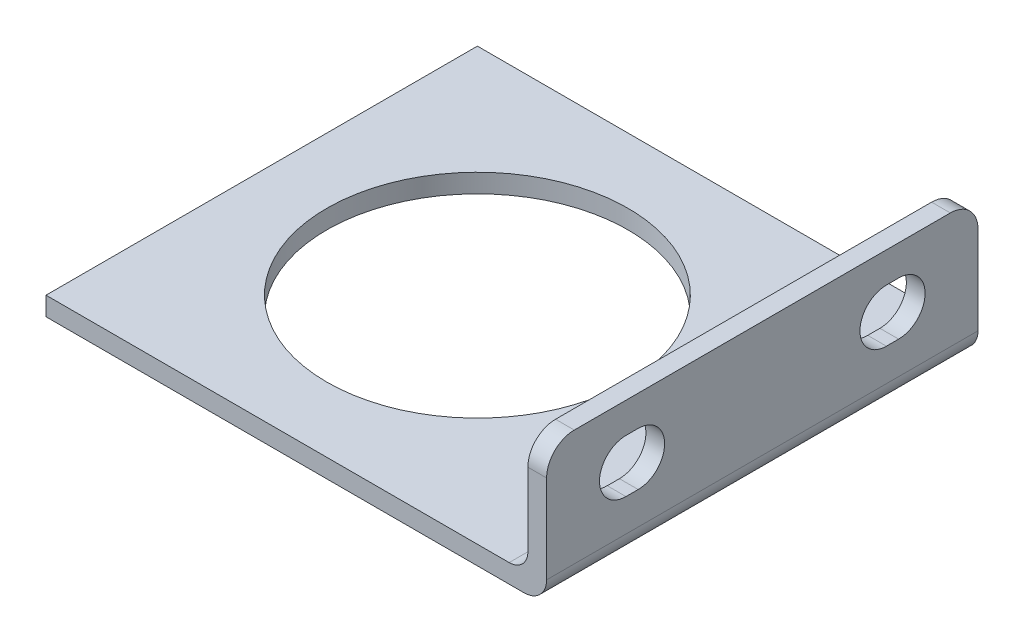
SolidWorks part; units mm, degrees
ref_plane "前视基准面" through (0, 0, 0) normal (0, 0, 1) x (1, 0, 0)
ref_plane "上视基准面" through (0, 0, 0) normal (0, 1, 0) x (1, 0, 0)
ref_plane "右视基准面" through (0, 0, 0) normal (1, 0, 0) x (0, 0, -1)
sketch "草图1" plane through (0, 0, 0) normal (0, 0, 1) x (1, 0, 0)
  line L0 (-26.5, 0) -> (32.24, 0)
  line L1 (35, 2.76) -> (35, 17)
  line L2 (35, 17) -> (32.7, 17)
  line L3 (32.7, 17) -> (32.7, 4.6)
  line L4 (30.4, 2.3) -> (-26.5, 2.3)
  line L5 (-26.5, 2.3) -> (-26.5, 0)
  arc A0 (32.24, 0) -> (35, 2.76) centre (32.24, 2.76) ccw
  arc A1 (32.7, 4.6) -> (30.4, 2.3) centre (30.4, 4.6) cw
extrude "凸台-拉伸1" add sketch "草图1" against normal blind 26.5 and the other way blind 26.5
ref_plane "基准面4" through (35, 0, 0) normal (1, 0, 0) x (0, 0, -1)
sketch "草图2" plane through (35, 0, 0) normal (1, 0, 0) x (0, 0, -1)
  line L0 (-16.75, 6.75) -> (-15.25, 6.75)
  line L1 (-15.25, 13.25) -> (-16.75, 13.25)
  arc A0 (-20, 10) -> (-16.75, 6.75) centre (-16.75, 10) ccw
  arc A1 (-15.25, 6.75) -> (-12, 10) centre (-15.25, 10) ccw
  arc A2 (-12, 10) -> (-15.25, 13.25) centre (-15.25, 10) ccw
  arc A3 (-16.75, 13.25) -> (-20, 10) centre (-16.75, 10) ccw
extrude "切除-拉伸1" cut sketch "草图2" against normal blind 2.3
sketch "草图3" plane through (35, 0, 0) normal (1, 0, 0) x (0, 0, -1)
  line L0 (15.25, 6.75) -> (16.75, 6.75)
  line L1 (16.75, 13.25) -> (15.25, 13.25)
  arc A0 (12, 10) -> (15.25, 6.75) centre (15.25, 10) ccw
  arc A1 (16.75, 6.75) -> (20, 10) centre (16.75, 10) ccw
  arc A2 (20, 10) -> (16.75, 13.25) centre (16.75, 10) ccw
  arc A3 (15.25, 13.25) -> (12, 10) centre (15.25, 10) ccw
extrude "切除-拉伸2" cut sketch "草图3" against normal blind 2.3
sketch "草图4" plane through (0, 0, 0) normal (0, 1, 0) x (1, 0, 0)
  circle A0 centre (0, 0) radius 18.5
extrude "切除-拉伸3" cut sketch "草图4" along normal blind 2.3
sketch "草图5" plane through (35, 0, 0) normal (1, 0, 0) x (0, 0, -1)
  line L0 (-67.1016, -37.4621) -> (75.136, -37.4621)
  line L1 (75.136, -37.4621) -> (75.136, 65.1989)
  line L2 (75.136, 65.1989) -> (-67.1016, 65.1989)
  line L3 (-67.1016, 65.1989) -> (-67.1016, -37.4621)
  line L4 (-26.5, 0) -> (26.5, 0)
  line L5 (26.5, 0) -> (26.5, 13.6)
  line L6 (23.1, 17) -> (-23.1, 17)
  line L7 (-26.5, 13.6) -> (-26.5, 0)
  arc A0 (26.5, 13.6) -> (23.1, 17) centre (23.1, 13.6) ccw
  arc A1 (-23.1, 17) -> (-26.5, 13.6) centre (-23.1, 13.6) ccw
extrude "切除-拉伸4" cut sketch "草图5" against normal blind 3.3
ref_plane "bracket_to_body XY" through (0, 0, 0) normal (0, 1, 0) x (1, 0, 0)
ref_plane "bracket_to_body XZ" through (0, 0, 0) normal (0, 0, 1) x (1, 0, 0)
ref_plane "bracket_to_body YZ" through (0, 0, 0) normal (1, 0, 0) x (0, 0, -1)
ref_axis "bracket_to_body X" through (-80.9, 0, 0) along (1, 0, 0)
ref_axis "bracket_to_body Y" through (0, 0, 50) along (0, 0, -1)
ref_axis "bracket_to_body Z" through (0, 50, 0) along (0, -1, 0)
sketch3d "bracket_to_body"
  point P0 (0, 0, 0)
